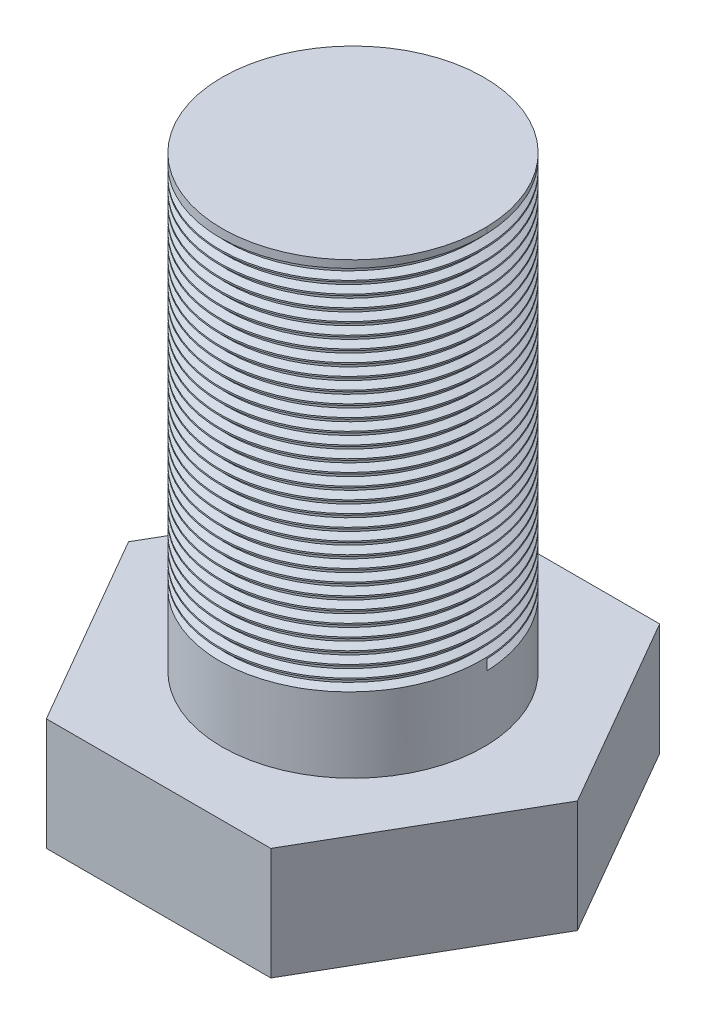
SolidWorks part; units mm, degrees
ref_plane "Front Plane" through (0, 0, 0) normal (0, 0, 1) x (1, 0, 0)
ref_plane "Top Plane" through (0, 0, 0) normal (0, 1, 0) x (1, 0, 0)
ref_plane "Right Plane" through (0, 0, 0) normal (1, 0, 0) x (0, 0, -1)
sketch "Sketch1" plane through (0, 0, 0) normal (0, 1, 0) x (1, 0, 0)
  line L1 (3, -5.1962) -> (6, 0)
  line L2 (6, 0) -> (3, 5.1962)
  line L3 (3, 5.1962) -> (-3, 5.1962)
  line L4 (-3, 5.1962) -> (-6, 0)
  line L5 (-6, 0) -> (-3, -5.1962)
  line L6 (-3, -5.1962) -> (3, -5.1962)
  circle A0 centre (0, 0) radius 5.1962 construction
  point P1 (19.0648, 0)
  dimension "D1" = 6
extrude "Boss-Extrude1" add sketch "Sketch1" along normal blind 3
sketch "Sketch2" plane through (0, 3, 0) normal (0, 1, 0) x (1, 0, 0)
  circle A0 centre (0, 0) radius 3.5
  dimension "D1" = 7
extrude "Boss-Extrude2" add sketch "Sketch2" along normal blind 12
thread "Thread1" pitch 0.3175 method cut profile "Thread Profile1" start angle 0, offset 0, length 10, pitch 0.3175, diameter 7
ref_plane "Plane1" through (-3.5, 15, 0) normal (0, 0, 1) x (-1, 0, 0)
sketch "Thread Profile1" plane through (-3.5, 15, 0) normal (0, 0, 1) x (-1, 0, 0)
  line L0 (0, 0) -> (0, 0.3175) construction
  line L11 (0, 0) -> (0, 0.2778)
  line L12 (0, 0.2778) -> (-0.1719, 0.1786)
  line L13 (-0.1719, 0.1786) -> (-0.1719, 0.0992)
  line L15 (-0.1719, 0.0992) -> (0, 0)
  line L17 (-0.1719, 0.1389) -> (0, 0.1389) construction
  point P2 (0, 0)
  dimension "Pitch" = 0.3175
  dimension "Profile_Angle" = 60
  dimension "Profile_Land" = 0.0794
  dimension "Profile_Height" = 0.1719
